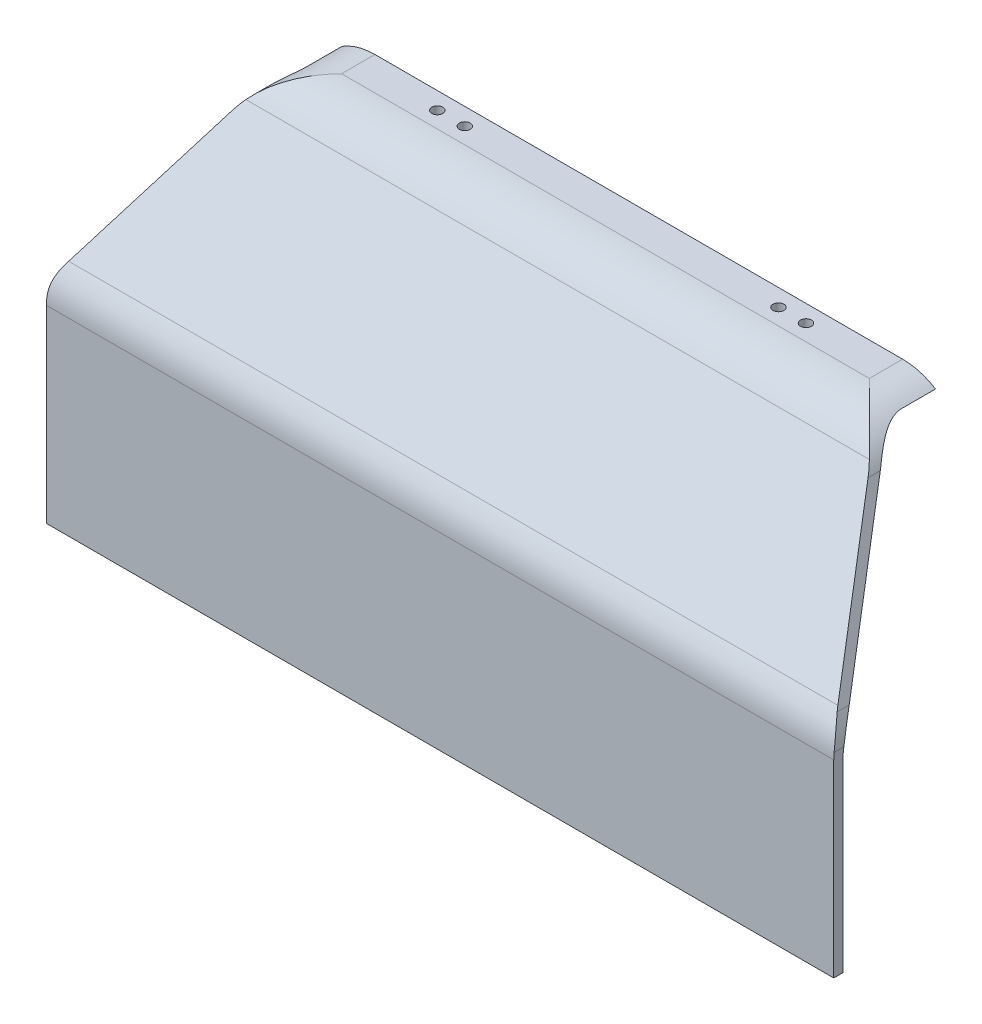
SolidWorks part; units mm, degrees
ref_plane "Alzado" through (0, 0, 0) normal (0, 0, 1) x (1, 0, 0)
ref_plane "Planta" through (0, 0, 0) normal (0, 1, 0) x (1, 0, 0)
ref_plane "Vista lateral" through (0, 0, 0) normal (1, 0, 0) x (0, 0, -1)
sketch "Croquis1" plane through (0, 0, 0) normal (1, 0, 0) x (0, 0, -1)
  line L0 (0, 0) -> (0, 66.9081)
  line L1 (0, 66.9081) -> (41.9998, 116.9615)
  line L2 (41.9998, 116.9615) -> (60.6009, 116.9615)
  line L3 (60.6009, 116.9615) -> (60.6009, 119.9615)
  line L4 (60.6009, 119.9615) -> (40.6009, 119.9615)
  line L5 (40.6009, 119.9615) -> (-3, 68)
  line L6 (-3, 68) -> (-3, 0)
  line L7 (-3, 0) -> (0, 0)
  line L8 (0, 66.9081) -> (29.2398, 66.9081) construction
  dimension "D1" = 3
  dimension "D2" = 3
  dimension "D3" = 3
  dimension "D4" = 68
  dimension "D5" = 119.9615
  dimension "D6" = 20
  dimension "D7" = 50
extrude "Saliente-Extruir1" add sketch "Croquis1" along normal mid plane 252
fillet "Redondeo1" radius 18 1 edges at (0, 68, 3)
fillet "Redondeo2" radius 20 1 edges at (0, 119.9615, -40.6009)
fillet "Redondeo3" radius 17 1 edges at (0, 116.9615, -41.9998)
fillet "Redondeo4" radius 17 1 edges at (0, 66.9081, 0)
sketch "Croquis2" plane through (0, 0, 3) normal (0, 0, 1) x (1, 0, 0)
  line L29 (-96, 119.9615) -> (-126, 68)
  line L35 (-96, 119.9615) -> (-126, 119.9615)
  line L36 (-126, 119.9615) -> (-126, 68)
  dimension "D5" = 60
extrude "Cortar-Extruir1" cut sketch "Croquis2" against normal through all
mirror "Simetría1" about plane through (0, 0, 0) normal (1, 0, 0) of "Cortar-Extruir1"
fillet "Redondeo5" radius 17 2 edges at (-126, 68, 0.064) (126, 68, 0.064)
sketch "Croquis5" plane through (0, 0, -60.6009) normal (0, 0, -1) x (-1, 0, 0)
  line L0 (84.453, 119.9615) -> (96, 119.9615)
  line L1 (96, 119.9615) -> (101.7735, 109.9615)
  arc A0 (101.7735, 109.9615) -> (84.453, 119.9615) centre (84.453, 99.9615) ccw
extrude "Cortar-Extruir2" cut sketch "Croquis5" against normal through all
mirror "Simetría2" about plane through (0, 0, 0) normal (1, 0, 0) of "Cortar-Extruir2"
sketch "Croquis6" plane through (0, 119.9615, 0) normal (0, 1, 0) x (1, 0, 0)
  circle A0 centre (-59, 55.1009) radius 1.75
  circle A1 centre (-50.2, 55.1009) radius 1.75
extrude "Cortar-Extruir3" cut sketch "Croquis6" against normal blind 20
mirror "Simetría3" about plane through (0, 0, 0) normal (1, 0, 0) of "Cortar-Extruir3"
sketch "Croquis7" plane through (0, 0, 0) normal (0, -1, 0) x (1, 0, 0)
  line L4 (-126, 3) -> (-126, 0)
  line L5 (-126, 0) -> (126, 0)
  line L6 (126, 0) -> (126, 3)
  line L7 (126, 3) -> (-126, 3)
  line L8 (-126, 3) -> (-126, 0)
  line L9 (-126, 0) -> (126, 0)
  line L10 (126, 0) -> (126, 3)
  line L11 (126, 3) -> (-126, 3)
  dimension "D1" = 0
extrude "Cortar-Extruir4" cut sketch "Croquis7" against normal blind 1
